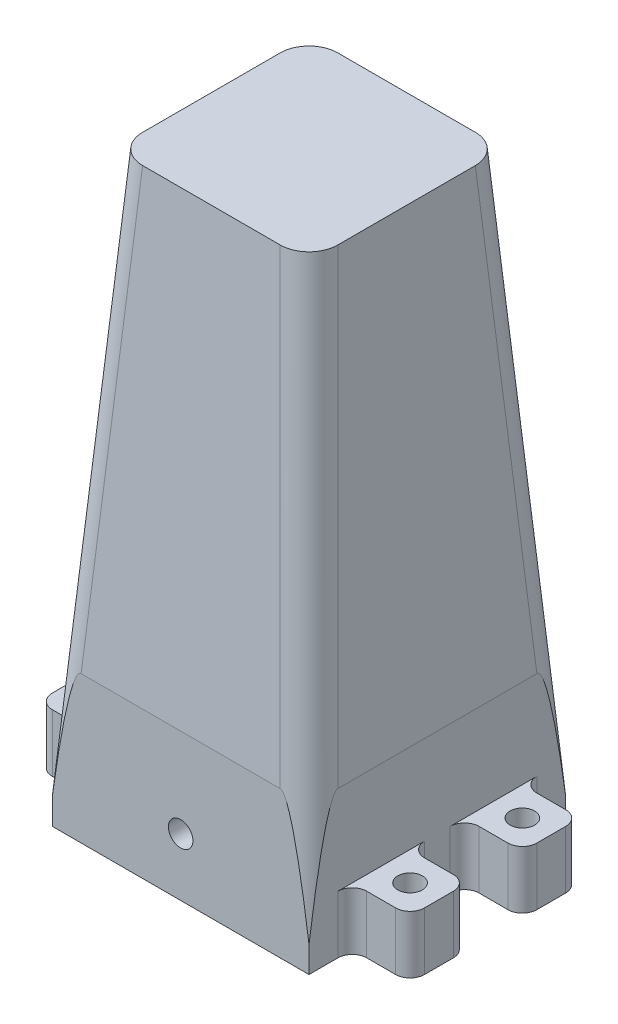
SolidWorks part; units mm, degrees
ref_plane "Front Plane" through (0, 0, 0) normal (0, 0, 1) x (1, 0, 0)
ref_plane "Top Plane" through (0, 0, 0) normal (0, 1, 0) x (1, 0, 0)
ref_plane "Right Plane" through (0, 0, 0) normal (1, 0, 0) x (0, 0, -1)
sketch "Sketch3" plane through (0, 0, 0) normal (0, 1, 0) x (1, 0, 0)
  line L1 (0, 0) -> (88.9, 0)
  line L2 (0, 0) -> (0, 88.9)
  line L3 (0, 88.9) -> (88.9, 88.9)
  line L4 (88.9, 0) -> (88.9, 88.9)
  dimension "D1" = 88.9
  dimension "D2" = 88.9
extrude "Boss-Extrude2" add sketch "Sketch3" along normal blind 50.8
ref_plane "Plane1" through (44.45, 0, 0) normal (-1, 0, 0) x (0, 0, 1)
sketch "Sketch5" plane through (0, 50.8, 0) normal (0, 1, 0) x (1, 0, 0)
  line L6 (0, 0) -> (88.9, 0)
  line L7 (0, 0) -> (0, 88.9)
  line L8 (0, 88.9) -> (88.9, 88.9)
  line L9 (88.9, 0) -> (88.9, 88.9)
extrude "Boss-Extrude3" add sketch "Sketch5" along normal blind 152.4 draft 4
fillet "Fillet1" [suppressed] radius 10
fillet "Fillet2" radius 10 4 edges at (83.5716, 127, -83.5716) (5.3284, 127, -83.5716) (83.5716, 127, -5.3284) (5.3284, 127, -5.3284)
sketch "Sketch7" plane through (0, 0, 0) normal (0, -1, 0) x (1, 0, 0)
  line L0 (44.45, -44.45) -> (64.45, -44.45)
  line L1 (44.45, 27.94) -> (44.45, -27.94) construction
  line L2 (64.45, -44.45) -> (64.45, -24.45)
  line L3 (64.45, -24.45) -> (24.45, -24.45)
  line L4 (24.45, -24.45) -> (24.45, -64.45)
  line L5 (24.45, -64.45) -> (64.45, -64.45)
  line L6 (64.45, -64.45) -> (64.45, -44.45)
  dimension "D1" = 20
  dimension "D2" = 20
  dimension "D3" = 40
  dimension "D4" = 40
extrude "Cut-Extrude1" cut sketch "Sketch7" against normal blind 41 contours L5 L6 L2 L3 L4 region at (63.8843, 0, -54.45)
sketch "Sketch10" plane through (0, 0, 0) normal (-1, 0, 0) x (0, 0, 1)
  line L0 (-78.9, 0) -> (-10, 0) construction
  line L1 (-73.9, 0) -> (-53.9, 0)
  line L2 (-73.9, 0) -> (-73.9, 20)
  line L3 (-73.9, 20) -> (-53.9, 20)
  line L4 (-53.9, 0) -> (-53.9, 20)
  line L5 (-88.9, 9.0584) -> (-88.9, 0) construction
  line L6 (-35, 0) -> (-15, 0)
  line L7 (-35, 0) -> (-35, 20)
  line L8 (-35, 20) -> (-15, 20)
  line L9 (-15, 0) -> (-15, 20)
  dimension "D1" = 20
  dimension "D2" = 20
  dimension "D3" = 20
  dimension "D4" = 20
  dimension "D5" = 18.9
  dimension "D6" = 15
sketch "Sketch11" plane through (88.9, 0, 0) normal (1, 0, 0) x (0, 0, -1)
  line L0 (10, 0) -> (78.9, 0) construction
  line L1 (15, 0) -> (35, 0)
  line L2 (15, 0) -> (15, 20)
  line L3 (15, 20) -> (35, 20)
  line L4 (35, 0) -> (35, 20)
  line L5 (0, 9.0584) -> (0, 0) construction
  line L6 (53.9, 0) -> (73.9, 0)
  line L7 (53.9, 0) -> (53.9, 20)
  line L8 (53.9, 20) -> (73.9, 20)
  line L9 (73.9, 0) -> (73.9, 20)
  line L10 (88.9, 9.0584) -> (88.9, 0) construction
  dimension "D1" = 20
  dimension "D2" = 20
  dimension "D3" = 15
  dimension "D4" = 15
extrude "Boss-Extrude4" add sketch "Sketch10" along normal blind 20
extrude "Boss-Extrude5" add sketch "Sketch11" along normal blind 20
sketch "Sketch12" plane through (0, 0, 0) normal (0, -1, 0) x (1, 0, 0)
  line L0 (-20, -35) -> (-20, -15) construction
  line L1 (-20, -15) -> (0, -15) construction
  line L2 (-20, -73.9) -> (-20, -53.9) construction
  line L3 (-20, -53.9) -> (0, -53.9) construction
  line L4 (108.9, -15) -> (88.9, -15) construction
  line L5 (108.9, -15) -> (108.9, -35) construction
  line L6 (108.9, -73.9) -> (88.9, -73.9) construction
  line L7 (108.9, -53.9) -> (108.9, -73.9) construction
  circle A0 centre (-10, -25) radius 4.25
  circle A1 centre (98.9, -25) radius 4.25
  circle A2 centre (98.9, -63.9) radius 4.25
  circle A3 centre (-10, -63.9) radius 4.25
  dimension "D1" = 10
  dimension "D2" = 10
  dimension "D3" = 10
  dimension "D4" = 10
  dimension "D5" = 10
  dimension "D6" = 10
  dimension "D7" = 10
  dimension "D8" = 10
extrude "Cut-Extrude3" cut sketch "Sketch12" against normal blind 20
fillet "Fillet3" radius 5 16 edges at (108.9, 10, -73.9) (88.9, 10, -73.9) (108.9, 10, -53.9) (88.9, 10, -53.9) (88.9, 10, -35) (108.9, 10, -35) (108.9, 10, -15) (88.9, 10, -15) (-20, 10, -15) (0, 10, -15) (-20, 10, -35) (0, 10, -35) (0, 10, -53.9) (-20, 10, -53.9) (0, 10, -73.9) (-20, 10, -73.9)
sketch "Sketch13" plane through (0, 0, 0) normal (0, 0, 1) x (1, 0, 0)
  line L0 (44.45, 27.94) -> (44.45, -27.94) construction
  line L1 (0, 0) -> (88.9, 0) construction
  line L2 (88.9, 9.0584) -> (88.9, 0) construction
  circle A0 centre (44.45, 20) radius 4.25
  dimension "D1" = 20
  dimension "D2" = 44.45
extrude "Cut-Extrude4" cut sketch "Sketch13" against normal blind 102
